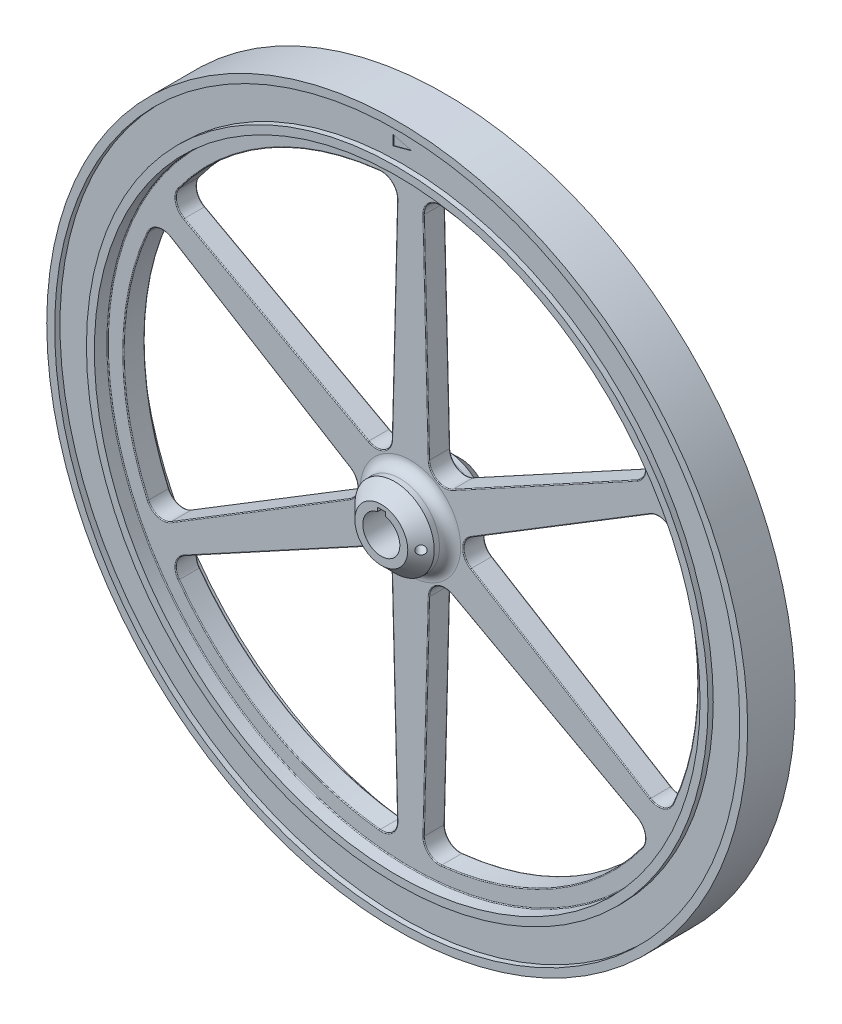
SolidWorks part; units mm, degrees
material "6061-T6 (SS)"
ref_plane "Front Plane" through (0, 0, 0) normal (0, 0, 1) x (1, 0, 0)
ref_plane "Top Plane" through (0, 0, 0) normal (0, 1, 0) x (1, 0, 0)
ref_plane "Right Plane" through (0, 0, 0) normal (1, 0, 0) x (0, 0, -1)
sketch "Sketch1" plane through (0, 0, 0) normal (0, 0, 1) x (1, 0, 0)
  circle A0 centre (0, 0) radius 114.5
  dimension "D1" = 229
extrude "Boss-Extrude1" add sketch "Sketch1" along normal mid plane 8
sketch "Sketch2" plane through (0, 0, 0) normal (0, 0, 1) x (1, 0, 0)
  circle A0 centre (0, 0) radius 15
  dimension "D1" = 30
extrude "Boss-Extrude2" add sketch "Sketch2" along normal mid plane 30
sketch "Sketch4" plane through (0, 0, 0) normal (0, 0, 1) x (1, 0, 0)
  circle A0 centre (0, 0) radius 114.5 construction
  circle A1 centre (0, 0) radius 114.5
  circle A2 centre (0, 0) radius 132.5
  dimension "D1" = 265
extrude "Boss-Extrude3" add sketch "Sketch4" along normal mid plane 18
sketch "Sketch6" plane through (0, 0, 9) normal (0, 0, 1) x (1, 0, 0)
  circle A0 centre (0, 0) radius 117.5
  circle A1 centre (0, 0) radius 129.5
  circle A2 centre (0, 0) radius 114.5 construction
  dimension "D1" = 12
  dimension "D2" = 3
extrude "Cut-Extrude1" cut sketch "Sketch6" against normal blind 2
mirror "Mirror1" about plane through (0, 0, 0) normal (0, 0, 1) of "Cut-Extrude1"
chamfer "Chamfer1" distance 5 2 edges at (15, 0, -15) (15, 0, 15)
sketch "Sketch7" plane through (0, 0, 15) normal (0, 0, 1) x (1, 0, 0)
  circle A0 centre (0, 0) radius 7
  dimension "D1" = 14
extrude "Cut-Extrude2" cut sketch "Sketch7" against normal up to next
sketch "Sketch8" plane through (0, 0, 0) normal (0, 0, 1) x (1, 0, 0)
  line L0 (0, 132.5) -> (0, -132.5) construction
  line L1 (-132.5, 0) -> (132.5, 0) construction
  line L2 (-66.25, 114.7484) -> (66.25, -114.7484) construction
  line L3 (66.25, 114.7484) -> (-66.25, -114.7484) construction
  line L4 (-114.7484, 66.25) -> (114.7484, -66.25) construction
  line L5 (114.7484, 66.25) -> (-114.7484, -66.25) construction
  line L6 (7.0019, 22.3656) -> (5.0019, 101.7569)
  line L7 (15.8682, 17.2466) -> (85.6231, 55.2102)
  circle A0 centre (0, 0) radius 26 construction
  circle A1 centre (0, 0) radius 132.5 construction
  arc A2 (7.0019, 22.3656) -> (15.8682, 17.2466) centre (13, 22.5167) ccw
  circle A3 centre (-13, 22.5167) radius 6 construction
  circle A4 centre (0, 0) radius 102.5 construction
  arc A5 (11.6439, 107.8734) -> (5.0019, 101.7569) centre (11, 101.908) ccw
  circle A6 centre (-11, 101.908) radius 6 construction
  arc A8 (87.5991, 64.0206) -> (85.6231, 55.2102) centre (82.755, 60.4803) cw
  arc A9 (11.6439, 107.8734) -> (87.5991, 64.0206) centre (0, 0) cw
  point P18 (0, 0)
  point P19 (0, 0)
  point P20 (0, 0)
  point P21 (0, 0)
  dimension "D6" = 12
  dimension "D8" = 205
  dimension "D2" = 30
  dimension "D3" = 30
  dimension "D4" = 30
  dimension "D5" = 13
  dimension "D7" = 11
extrude "Cut-Extrude3" cut sketch "Sketch8" against normal through all both and the other way through all
pattern_circular "CirPattern1" count 6 over 360 about axis through (0, 0, 4) along (0, 0, -1) of "Cut-Extrude3"
fillet "Fillet1" radius 4 2 edges at (15, 0, -4) (15, 0, 4)
sketch "Sketch9" plane through (0, 0, 0) normal (0, 0, 1) x (1, 0, 0)
  line L0 (0, 7) -> (0, 10) construction
  line L1 (-1.5, 6.8374) -> (-1.5, 8.3374)
  line L2 (-1.5, 8.3374) -> (1.5, 8.3374)
  line L3 (1.5, 8.3374) -> (1.5, 6.8374)
  circle A0 centre (0, 0) radius 7 construction
  circle A1 centre (0, 0) radius 10 construction
  arc A2 (1.5, 6.8374) -> (-1.5, 6.8374) centre (0, 0) ccw
  dimension "D1" = 3
  dimension "D2" = 1.5
extrude "Cut-Extrude4" cut sketch "Sketch9" against normal through all both and the other way through all
fillet "Fillet2" radius 0.3 74 edges at (-95.5451, -47.1545, -4) (-108.5, 0, -4) (-95.5451, 47.1545, -4) (-56.7476, 25.8328, -4) (-20, 0, -4) (-88.6095, 59.1672, -4) (-54.25, 93.9638, -4) (-6.9356, 106.3217, -4) (-6.0019, 62.0613, -4) (-10, 17.3205, -4) (6.9356, 106.3217, -4) (54.25, 93.9638, -4) (88.6095, 59.1672, -4) (50.7457, 36.2284, -4) (10, 17.3205, -4) (95.5451, 47.1545, -4) (108.5, 0, -4) (95.5451, -47.1545, -4) (56.7476, -25.8328, -4) (20, 0, -4) (10, -17.3205, -4) (50.7457, -36.2284, -4) (88.6095, -59.1672, -4) (54.25, -93.9638, -4) (6.9356, -106.3217, -4) (-10, -17.3205, -4) (-6.0019, -62.0613, -4) (-6.9356, -106.3217, -4) (-54.25, -93.9638, -4) (-88.6095, -59.1672, -4) (6.9356, 106.3217, 4) (54.25, 93.9638, 4) (88.6095, 59.1672, 4) (50.7457, 36.2284, 4) (10, 17.3205, 4) (-88.6095, 59.1672, 4) (-54.25, 93.9638, 4) (-6.9356, 106.3217, 4) (-6.0019, 62.0613, 4) (-10, 17.3205, 4) (-20, 0, 4) (-56.7476, -25.8328, 4) (-95.5451, -47.1545, 4) (-108.5, 0, 4) (-95.5451, 47.1545, 4) (-10, -17.3205, 4) (-6.0019, -62.0613, 4) (-6.9356, -106.3217, 4) (-54.25, -93.9638, 4) (-88.6095, -59.1672, 4) (10, -17.3205, 4) (50.7457, -36.2284, 4) (88.6095, -59.1672, 4) (54.25, -93.9638, 4) (6.9356, -106.3217, 4) (20, 0, 4) (56.7476, 25.8328, 4) (95.5451, 47.1545, 4) (108.5, 0, 4) (95.5451, -47.1545, 4) (114.5, 0, 4) (114.5, 0, -4) (-56.7476, -25.8328, -4) (-50.7457, 36.2284, -4) (6.0019, 62.0613, -4) (56.7476, 25.8328, -4) (6.0019, -62.0613, -4) (-50.7457, -36.2284, -4) (6.0019, 62.0613, 4) (-50.7457, 36.2284, 4) (-56.7476, 25.8328, 4) (-50.7457, -36.2284, 4) (6.0019, -62.0613, 4) (56.7476, -25.8328, 4)
sketch "Sketch11" plane through (0, 0, 0) normal (0, 1, 0) x (1, 0, 0)
  line L0 (0, -0.0008) -> (12.4996, -12.5004) construction
  line L1 (10, -15) -> (15, -10) construction
  line L2 (0, -0.0008) -> (12.4996, -0.0008) construction
  line L3 (0, -0.0008) -> (12.5004, 12.4996) construction
  line L4 (15, 10) -> (10, 15) construction
  dimension "D1" = 3.535
ref_plane "Plane1" through (12.4996, 0, 12.5004) normal (0.7071, 0, 0.7071) x (0.7071, 0, -0.7071)
hole_wizard "M4x0.7 Tapped Hole2" positions "Sketch12" profile "Sketch13" tap size "M4x0.7" standard "ANSI Metric" end condition up to next
sketch "Sketch12" plane through (12.4996, 0, 12.5004) normal (0.7071, 0, 0.7071) x (0.7071, 0, -0.7071)
  point P0 (0, 0)
sketch "Sketch13" plane through (12.4996, 0, 12.5004) normal (0, 1, 0) x (0.7071, 0, -0.7071)
  line L0 (0, 0) -> (0, 7.7776)
  line L1 (0, 7.7776) -> (1.65, 7.7776)
  line L2 (1.65, 7.7776) -> (1.65, 0)
  line L5 (1.65, 0) -> (0, 0)
  line L11 (0, -6.35) -> (0, 107.95) construction
  dimension "Thru Tap Drill Dia." = 3.3
  dimension "Thru Tap Drill Depth" = 7.7776
cosmetic thread "Hole Thread2"
ref_plane "Plane2" through (12.5004, 0, -12.4996) normal (-0.7071, 0, 0.7071) x (0.7071, 0, 0.7071)
hole_wizard "M4x0.7 Tapped Hole6" positions "Sketch20" profile "Sketch21" tap size "M4x0.7" standard "ANSI Metric" end condition up to next
sketch "Sketch20" plane through (12.5004, 0, -12.4996) normal (-0.7071, 0, 0.7071) x (0.7071, 0, 0.7071)
  point P0 (0, 0)
sketch "Sketch21" plane through (12.5004, 0, -12.4996) normal (0, 1, 0) x (-0.7071, 0, -0.7071)
  line L0 (0, 0) -> (0, 7.7787)
  line L1 (0, 7.7787) -> (1.65, 7.7787)
  line L2 (1.65, 7.7787) -> (1.65, 0)
  line L5 (1.65, 0) -> (0, 0)
  line L11 (0, -6.35) -> (0, 107.95) construction
  dimension "Thru Tap Drill Dia." = 3.3
  dimension "Thru Tap Drill Depth" = 7.7787
cosmetic thread "Hole Thread5"
sketch "Sketch22" plane through (0, 0, 7) normal (0, 0, 1) x (1, 0, 0)
  line L0 (0, 117.5) -> (0, 129.5) construction
  line L1 (3.5, 123.5) -> (-3.5, 125.3756)
  line L2 (-3.5, 125.3756) -> (-3.5, 121.6244)
  line L3 (-3.5, 121.6244) -> (3.5, 123.5)
  line L4 (-3.5, 123.5) -> (3.5, 123.5) construction
  circle A0 centre (0, 0) radius 117.5 construction
  circle A1 centre (0, 0) radius 129.5 construction
  point P11 (0, 123.5)
  point P12 (0, 123.5)
  dimension "D1" = 7
  dimension "D2" = 30
extrude "Cut-Extrude5" cut sketch "Sketch22" against normal blind 0.2
mirror "Mirror4" about plane through (0, 0, 0) normal (0, 0, 1) of "Cut-Extrude5"
